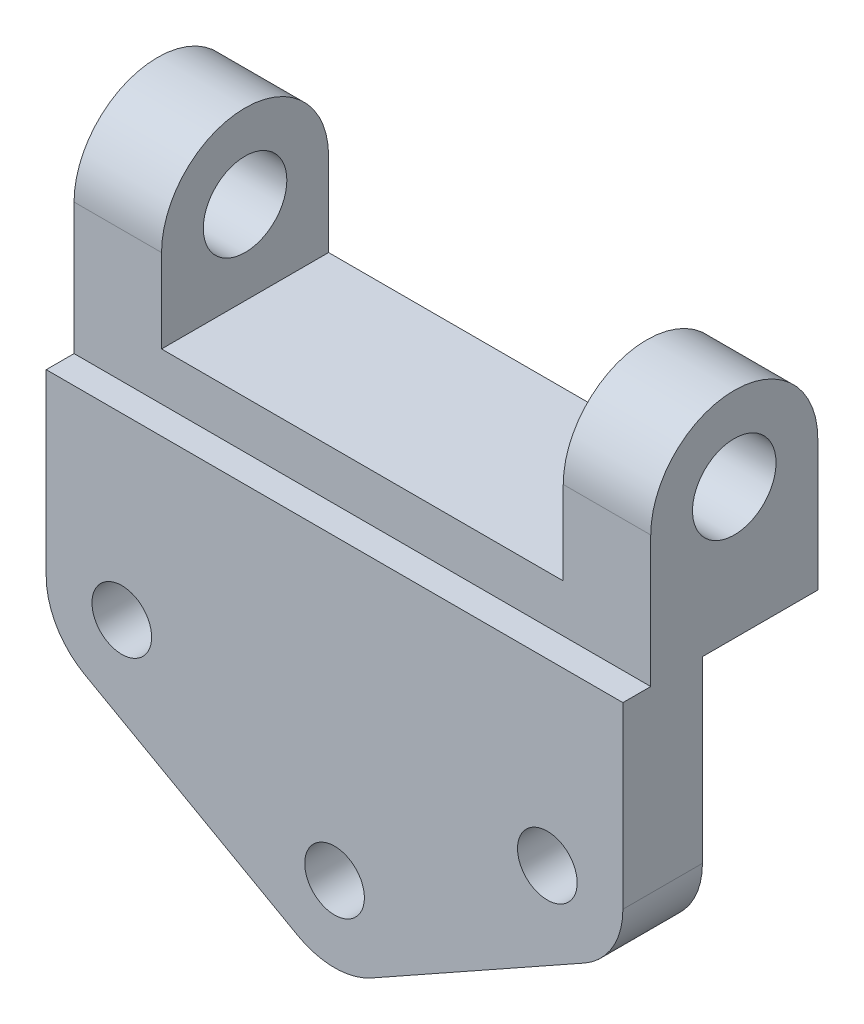
SolidWorks part; units mm, degrees
ref_plane "Front Plane" through (0, 0, 0) normal (0, 0, 1) x (1, 0, 0)
ref_plane "Top Plane" through (0, 0, 0) normal (0, 1, 0) x (1, 0, 0)
ref_plane "Right Plane" through (0, 0, 0) normal (1, 0, 0) x (0, 0, -1)
sketch "Sketch1" plane through (0, 0, 0) normal (0, 0, 1) x (1, 0, 0)
  line L0 (0, -87) -> (0, 87) construction
  line L1 (50.5, 0) -> (-50.5, 0)
  line L2 (-50.5, 0) -> (-50.5, 54)
  line L3 (-50.5, 54) -> (-72.5, 54)
  line L4 (-72.5, 54) -> (-72.5, -57)
  line L5 (-62.7929, -73.5723) -> (-9.2929, -103.5723)
  line L6 (72.5, -12) -> (-72.5, -12)
  line L7 (62.7929, -73.5723) -> (9.2929, -103.5723)
  line L8 (72.5, 54) -> (72.5, -57)
  line L9 (50.5, 54) -> (72.5, 54)
  line L10 (50.5, 0) -> (50.5, 54)
  line L11 (-50.5, 0) -> (-72.5, 0)
  line L12 (50.5, 0) -> (72.5, 0)
  arc A0 (-72.5, -57) -> (-62.7929, -73.5723) centre (-53.5, -57) ccw
  arc A1 (-9.2929, -103.5723) -> (9.2929, -103.5723) centre (0, -87) ccw
  circle A2 centre (-53.5, -57) radius 7.5
  circle A3 centre (0, -87) radius 7.5
  circle A4 centre (53.5, -57) radius 7.5
  arc A5 (72.5, -57) -> (62.7929, -73.5723) centre (53.5, -57) cw
  point P4 (0, 0)
  point P22 (0, -12)
  point P25 (0, 0)
  dimension "D7" = 19
  dimension "D8" = 19
  dimension "D9" = 15
  dimension "D10" = 15
  dimension "D1" = 101
  dimension "D2" = 12
  dimension "D3" = 145
  dimension "D4" = 45
  dimension "D5" = 54
  dimension "D6" = 75
extrude "Boss-Extrude1" add sketch "Sketch1" along normal blind 20 contours A3 L6 L4 A0 L5 A1 L7 A5 L8 A2 A4 region at (0, -50.1718, 0)
extrude "Boss-Extrude3" add sketch "Sketch1<4>" along normal mid plane 60 contours L11 L2 L3 L4 | L10 L12 L8 L9 | L6 L0 L1 L11 L4 | L0 L6 L8 L12 L1 region at (-36.25, -6, 0) region at (36.25, -6, 0) region at (61.5, 27, 0) region at (-61.5, 27, 0)
sketch "Sketch1<4>" plane through (0, 0, 0) normal (0, 0, 1) x (1, 0, 0) same geometry as "Sketch1"
sketch "Sketch5" plane through (72.5, 0, 0) normal (1, 0, 0) x (0, 0, -1)
  line L0 (-13, 21) -> (-13, -12)
  line L1 (-13, -12) -> (30, -12)
  line L2 (30, 54) -> (-30, 54)
  line L3 (-30, 54) -> (-30, -12)
  line L4 (-30, -12) -> (-13, -12)
  line L5 (29, 21) -> (29, -12)
  line L6 (-30, -12) -> (30, -12)
  line L7 (30, -12) -> (30, 54)
  line L8 (-20, -12) -> (-20, -57) construction
  line L9 (-13, -12) -> (29, -12)
  circle A0 centre (8, 21) radius 21
  circle A1 centre (8, 21) radius 10.5
  point P3 (-13, 21)
  line M6 (30, -12) -> (30, 54)
  line M7 (30, 54) -> (-30, 54)
  line M8 (-30, 54) -> (-30, -12)
  line M9 (-30, -12) -> (-20, -12)
  dimension "D1" = 21
  dimension "D2" = 42
  dimension "D3" = 7
  dimension "D4" = 33
extrude "Cut-Extrude6" cut sketch "Sketch5" against normal up to surface (145 mm away) contours A0 L5 L1 L4 L0 M6 M7 M8 M9 | A1 region at (72.5, 4.5, 13.892) up to face at (-72.5, -6.75, 5)
